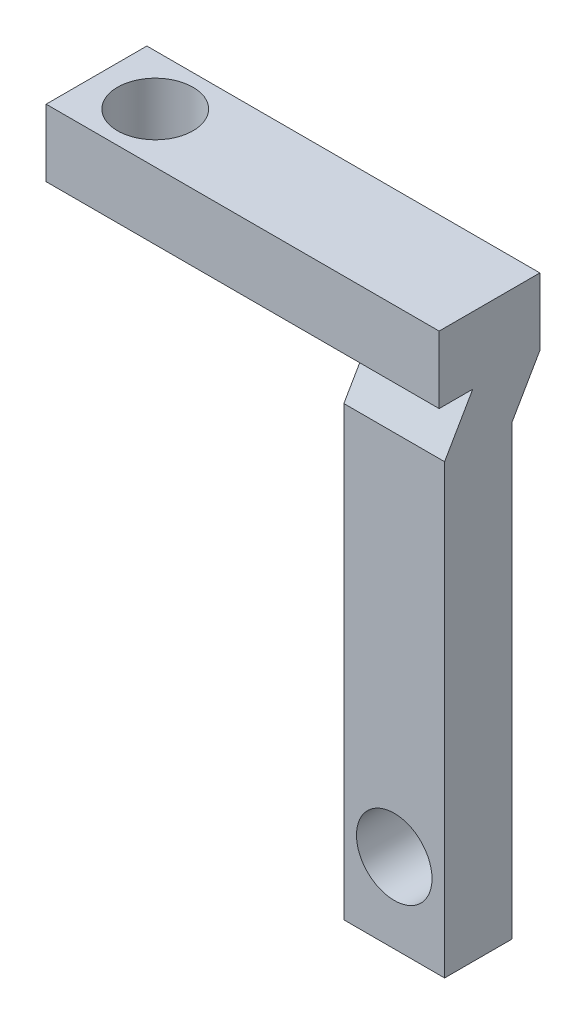
SolidWorks part; units mm, degrees
note: The reader was unsure of these and kept them because the rebuilt part matched: shared geometry of "Sketch1<3>".
ref_plane "Front Plane" through (0, 0, 0) normal (0, 0, 1) x (1, 0, 0)
ref_plane "Top Plane" through (0, 0, 0) normal (0, 1, 0) x (1, 0, 0)
ref_plane "Right Plane" through (0, 0, 0) normal (1, 0, 0) x (0, 0, -1)
sketch "Sketch1" plane through (0, 0, 0) normal (1, 0, 0) x (0, 0, -1)
  line L0 (471.916, 0) -> (483.916, 0)
  line L1 (772.2979, 0) -> (-772.2979, 0) construction
  line L2 (483.916, -8) -> (483.916, 0)
  line L3 (471.916, 0) -> (471.916, -8)
  line L4 (471.916, -8) -> (475.916, -8)
  line L7 (475.916, -8) -> (483.916, -8)
  line L8 (480.566, -67.07) -> (472.566, -67.07)
  line L10 (472.566, -67.07) -> (472.566, -13.8024)
  line L11 (480.566, -67.07) -> (480.566, -13.8024)
  line L14 (475.916, -8) -> (472.566, -13.8024)
  line L16 (483.916, -8) -> (480.566, -13.8024)
  dimension "D1" = 3.35
  dimension "D2" = 8
  dimension "D3" = 12
  dimension "D4" = 8
  dimension "D5" = 60
  dimension "D6" = 60
extrude "Boss-Extrude1" add sketch "Sketch1" against normal blind 12
extrude "Boss-Extrude2" add sketch "Sketch1<3>" against normal blind 46.82 contours L4 L7 L2 L0 L3
sketch "Sketch1<3>" plane through (0, 0, 0) normal (1, 0, 0) x (0, 0, -1) same geometry as "Sketch1"
sketch "Sketch3" plane through (0, -8, 0) normal (0, -1, 0) x (1, 0, 0)
  line L0 (-46.82, -477.916) -> (-12, -477.916) construction
  line L1 (-46.82, -471.916) -> (-46.82, -483.916) construction
  line L3 (-46.82, -471.916) -> (-46.82, -483.916) construction
  line L4 (-12, -475.916) -> (-12, -483.916) construction
  circle A0 centre (-39.82, -477.916) radius 4.5
  dimension "D1" = 7
extrude "Cut-Extrude2" cut sketch "Sketch3" along direction (0, -1, 0) on the side against the normal up to next (8 mm away)
sketch "Sketch5" plane through (0, 0, -472.566) normal (0, 0, 1) x (1, 0, 0)
  line L0 (-6, -67.07) -> (-6, -13.8024) construction
  line L1 (-12, -67.07) -> (0, -67.07) construction
  line L2 (-12, -13.8024) -> (0, -13.8024) construction
  circle A0 centre (-6, -57.57) radius 4.5
  dimension "D1" = 9.5
extrude "Cut-Extrude4" cut sketch "Sketch5" against normal up to surface (8 mm away) up to face at (-6, -40.4362, -480.566)
